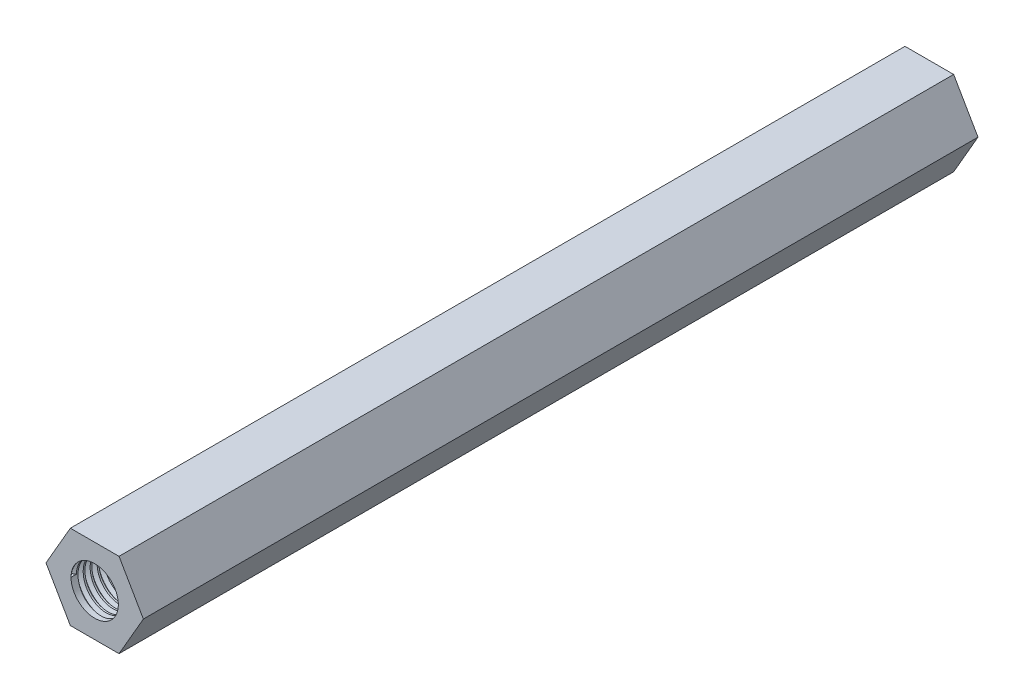
SolidWorks part; units mm, degrees
material "1.7036 (28CrS4)"
ref_plane "Plan de face" through (0, 0, 0) normal (0, 0, 1) x (1, 0, 0)
ref_plane "Plan de dessus" through (0, 0, 0) normal (0, 1, 0) x (1, 0, 0)
ref_plane "Plan de droite" through (0, 0, 0) normal (1, 0, 0) x (0, 0, -1)
sketch "Esquisse1" plane through (0, 0, 0) normal (0, 0, 1) x (1, 0, 0)
  line L0 (0, 3.5) -> (7, 3.5) construction
  line L1 (0, 0) -> (7, 0) construction
  line L2 (0, 0) -> (0, 7) construction
  line L3 (0, 7) -> (7, 7) construction
  line L4 (7, 0) -> (7, 7) construction
  line L5 (3.5, 7) -> (3.5, 0) construction
  line L7 (5.25, 0.4689) -> (7, 3.5)
  line L8 (7, 3.5) -> (5.25, 6.5311)
  line L9 (5.25, 6.5311) -> (1.75, 6.5311)
  line L10 (1.75, 6.5311) -> (0, 3.5)
  line L11 (0, 3.5) -> (1.75, 0.4689)
  line L12 (1.75, 0.4689) -> (5.25, 0.4689)
  circle A0 centre (3.5, 3.5) radius 3.5 construction
  dimension "D3" = 7
  dimension "D1" = 7
  dimension "D2" = 7
extrude "Boss.-Extru.1" add sketch "Esquisse1" along normal blind 60
sketch "Esquisse2" plane through (0, 0, 60) normal (0, 0, 1) x (1, 0, 0)
  line L0 (3.5, 6.5311) -> (3.5, 0.4689) construction
  line L1 (0.875, 1.9845) -> (6.125, 5.0155) construction
  line L6 (1.75, 0.4689) -> (5.25, 0.4689)
  line L7 (5.25, 0.4689) -> (7, 3.5)
  line L8 (7, 3.5) -> (5.25, 6.5311)
  line L9 (5.25, 6.5311) -> (1.75, 6.5311)
  line L10 (1.75, 6.5311) -> (0, 3.5)
  line L11 (0, 3.5) -> (1.75, 0.4689)
  line L12 (1.75, 0.4689) -> (5.25, 0.4689)
  line L13 (5.25, 0.4689) -> (7, 3.5)
  line L14 (7, 3.5) -> (5.25, 6.5311)
  line L15 (5.25, 6.5311) -> (1.75, 6.5311)
  line L16 (1.75, 6.5311) -> (0, 3.5)
  line L17 (0, 3.5) -> (1.75, 0.4689)
  circle A0 centre (3.5, 3.5) radius 1.5
  dimension "D2" = 3
  dimension "D1" = 0
hole_wizard "Dégagement M31" positions "Esquisse6" profile "Esquisse7" hole size "M3" standard "ISO"
sketch "Esquisse6" plane through (0, 0, 60) normal (0, 0, 1) x (1, 0, 0)
  point P0 (3.5, 3.5)
sketch "Esquisse7" plane through (3.5, 3.5, 60) normal (1, 0, 0) x (0, -1, 0)
  line L0 (0, 0) -> (0, 16.0215)
  line L1 (0, 16.0215) -> (1.7, 15)
  line L2 (1.7, 15) -> (1.7, 0)
  line L5 (1.7, 0) -> (0, 0)
  line L10 (0, 16.0215) -> (-1.7, 15) construction
  line L11 (0, -6.35) -> (0, 107.95) construction
  dimension "Diamètre du perçage" = 3.4
  dimension "Profondeur du perçage" = 15
  dimension "Angle de pointe" = 118
thread "Filetage1" pitch 0.5 method cut profile "Profil de filetage1" start angle 0, offset 0, length 15, pitch 0.5, diameter 3.4
ref_plane "Plan1" through (1.8, 3.5, 60) normal (0, -1, 0) x (-1, 0, 0)
sketch "Profil de filetage1" plane through (1.8, 3.5, 60) normal (0, -1, 0) x (-1, 0, 0)
  line L0 (0, 0) -> (0, 0.5) construction
  line L1 (0, 0) -> (0.2706, 0.1562)
  line L2 (0.2706, 0.1562) -> (0.2706, 0.2187)
  line L3 (0.2706, 0.2187) -> (0, 0.375)
  line L4 (0.2706, 0.1875) -> (0, 0.1875) construction
  line L11 (0, 0) -> (0, 0.375)
  point P2 (0, 0)
  dimension "Pitch" = 0.5
  dimension "Profile_Angle" = 60
  dimension "Profile_Land" = 0.0625
  dimension "Profile_Height" = 0.2706
hole_wizard "Dégagement M32" positions "Esquisse10" profile "Esquisse11" hole size "M3" standard "ISO"
sketch "Esquisse10" plane through (0, 0, 0) normal (0, 0, -1) x (-1, 0, 0)
  point P0 (-3.5, 3.5)
sketch "Esquisse11" plane through (3.5, 3.5, 0) normal (1, 0, 0) x (0, 1, 0)
  line L0 (0, 0) -> (0, 9.0215)
  line L1 (0, 9.0215) -> (1.7, 8)
  line L2 (1.7, 8) -> (1.7, 0)
  line L5 (1.7, 0) -> (0, 0)
  line L10 (0, 9.0215) -> (-1.7, 8) construction
  line L11 (0, -6.35) -> (0, 107.95) construction
  dimension "Diamètre du perçage" = 3.4
  dimension "Profondeur du perçage" = 8
  dimension "Angle de pointe" = 118
sketch "Esquisse12" plane through (0, 0, 0) normal (0, 0, -1) x (-1, 0, 0)
  line L6 (-5.25, 0.4689) -> (-1.75, 0.4689)
  line L7 (-1.75, 0.4689) -> (0, 3.5)
  line L8 (0, 3.5) -> (-1.75, 6.5311)
  line L9 (-1.75, 6.5311) -> (-5.25, 6.5311)
  line L10 (-5.25, 6.5311) -> (-7, 3.5)
  line L11 (-7, 3.5) -> (-5.25, 0.4689)
  line L12 (-5.25, 0.4689) -> (-1.75, 0.4689)
  line L13 (-1.75, 0.4689) -> (0, 3.5)
  line L14 (0, 3.5) -> (-1.75, 6.5311)
  line L15 (-1.75, 6.5311) -> (-5.25, 6.5311)
  line L16 (-5.25, 6.5311) -> (-7, 3.5)
  line L17 (-7, 3.5) -> (-5.25, 0.4689)
  circle A0 centre (-3.5, 3.5) radius 1.5
  dimension "D2" = 3
  dimension "D1" = 0
extrude "Enlèv. mat.-Extru.1" [suppressed] cut sketch "Esquisse12" against normal blind 15
thread "Filetage2" pitch 0.5 method cut profile "Profil de filetage2" start angle 0, offset 0, length 10, pitch 0.5, diameter 3.4
ref_plane "Plan2" through (5.2, 3.5, 0) normal (0, -1, 0) x (1, 0, 0)
sketch "Profil de filetage2" plane through (5.2, 3.5, 0) normal (0, -1, 0) x (1, 0, 0)
  line L0 (0, 0) -> (0, 0.5) construction
  line L1 (0, 0) -> (0.2706, 0.1562)
  line L2 (0.2706, 0.1562) -> (0.2706, 0.2187)
  line L3 (0.2706, 0.2187) -> (0, 0.375)
  line L4 (0.2706, 0.1875) -> (0, 0.1875) construction
  line L11 (0, 0) -> (0, 0.375)
  point P2 (0, 0)
  dimension "Pitch" = 0.5
  dimension "Profile_Angle" = 60
  dimension "Profile_Land" = 0.0625
  dimension "Profile_Height" = 0.2706
equation "\"diam_cercle_circons\"= 7"
equation "\"D1@Esquisse1\"=\"diam_cercle_circons\""
equation "\"D2@Esquisse1\"=\"diam_cercle_circons\""
equation "\"Hauteur\"= 60"
equation "\"D1@Boss.-Extru.1\"=\"Hauteur\""
equation "\"D3@Esquisse1\"=\"diam_cercle_circons\""
